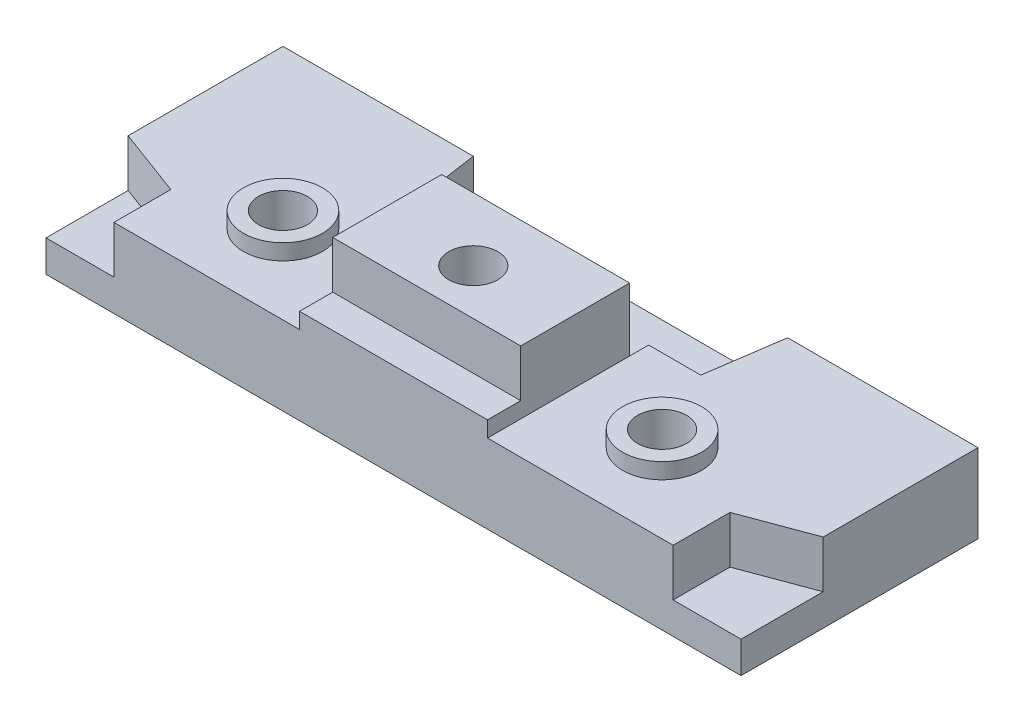
SolidWorks part; units mm, degrees
ref_plane "Front Plane" through (0, 0, 0) normal (0, 0, 1) x (1, 0, 0)
ref_plane "Top Plane" through (0, 0, 0) normal (0, 1, 0) x (1, 0, 0)
ref_plane "Right Plane" through (0, 0, 0) normal (1, 0, 0) x (0, 0, -1)
sketch "Sketch1" plane through (0, 0, 0) normal (0, 1, 0) x (1, 0, 0)
  line L1 (0, 0) -> (44, 0)
  line L2 (0, 0) -> (0, -15)
  line L3 (0, -15) -> (44, -15)
  line L4 (44, 0) -> (44, -15)
  dimension "D1" = 15
  dimension "D2" = 44
extrude "Boss-Extrude1" add sketch "Sketch1" along normal blind 5
sketch "Sketch2" plane through (0, 5, 0) normal (0, 1, 0) x (1, 0, 0)
  line L0 (44, 0) -> (0, 0) construction
  line L1 (16.05, 0) -> (27.95, 0)
  line L2 (16.05, 0) -> (16.05, -15)
  line L3 (16.05, -15) -> (27.95, -15)
  line L4 (27.95, 0) -> (27.95, -15)
  line L5 (0, -15) -> (44, -15) construction
  line L6 (22, 0) -> (22, -15) construction
  dimension "D1" = 5.95
  dimension "D2" = 5.95
extrude "Boss-Extrude2" add sketch "Sketch2" along normal blind 4
sketch "Sketch3" plane through (0, 5, 0) normal (0, 1, 0) x (1, 0, 0)
  line L0 (0, -15) -> (16.05, -15) construction
  line L1 (16.05, 0) -> (16.05, -15) construction
  line L2 (27.95, -15) -> (27.95, 0) construction
  line L3 (27.95, -15) -> (44, -15) construction
  circle A0 centre (10, -10) radius 1.55
  circle A1 centre (34, -10) radius 1.55
  dimension "D1" = 3.1
  dimension "D3" = 3.1
  dimension "D2" = 5
  dimension "D4" = 5
  dimension "D5" = 6.05
  dimension "D6" = 6.05
extrude "Cut-Extrude1" cut sketch "Sketch3" against normal blind 3
sketch "Sketch4" plane through (0, 9, 0) normal (0, 1, 0) x (1, 0, 0)
  line L1 (16.05, -15) -> (27.95, -15) construction
  line L2 (16.05, 0) -> (16.05, -15) construction
  circle A0 centre (22.05, -10) radius 1.55
  dimension "D1" = 3.1
  dimension "D2" = 5
  dimension "D3" = 6
extrude "Cut-Extrude2" cut sketch "Sketch4" against normal blind 3
sketch "Sketch5" plane through (0, 5, 0) normal (0, 1, 0) x (1, 0, 0)
  line L0 (22, 0) -> (22, -15) construction
  line L1 (27.95, 0) -> (16.05, 0) construction
  line L2 (16.05, -15) -> (27.95, -15) construction
  circle A0 centre (10, -10) radius 2.5
  circle A1 centre (10, -10) radius 1.55
  circle A2 centre (34, -10) radius 2.5
  circle A3 centre (34, -10) radius 1.55
  dimension "D1" = 5
extrude "Boss-Extrude3" add sketch "Sketch5" along normal blind 1
sketch "Sketch6" plane through (0, 5, 0) normal (0, 1, 0) x (1, 0, 0)
  line L0 (16.05, -4.8) -> (12.75, -4.8)
  line L1 (16.05, 0) -> (16.05, -15) construction
  line L2 (12.75, -4.8) -> (12.05, 0)
  line L3 (16.05, 0) -> (0, 0) construction
  line L4 (12.05, 0) -> (16.05, 0)
  line L5 (16.05, 0) -> (16.05, -4.8)
  line L6 (0, -15) -> (4.3, -15)
  line L7 (0, -15) -> (16.05, -15) construction
  line L8 (4.3, -15) -> (4.3, -11.4)
  line L9 (4.3, -11.4) -> (0, -9.8)
  line L10 (0, 0) -> (0, -15) construction
  line L11 (0, -9.8) -> (0, -15)
  line L12 (22, 0) -> (22, -15) construction
  line L13 (27.95, 0) -> (16.05, 0) construction
  line L14 (16.05, -15) -> (27.95, -15) construction
  line L15 (39.7, -11.4) -> (44, -9.8)
  line L16 (39.7, -15) -> (39.7, -11.4)
  line L17 (44, -15) -> (39.7, -15)
  line L18 (44, -9.8) -> (44, -15)
  line L19 (31.95, 0) -> (27.95, 0)
  line L20 (31.25, -4.8) -> (31.95, 0)
  line L21 (27.95, -4.8) -> (31.25, -4.8)
  line L22 (27.95, 0) -> (27.95, -4.8)
  dimension "D1" = 4.8
  dimension "D2" = 3.3
  dimension "D3" = 4
  dimension "D4" = 4.3
  dimension "D5" = 3.6
  dimension "D6" = 5.2
extrude "Cut-Extrude3" cut sketch "Sketch6" against normal blind 3
sketch "Sketch7" plane through (0, 9, 0) normal (0, 1, 0) x (1, 0, 0)
  line L0 (27.95, -15) -> (27.95, 0) construction
  line L1 (16.05, 0) -> (27.95, 0)
  line L2 (16.05, 0) -> (16.05, -6)
  line L3 (16.05, -6) -> (27.95, -6)
  line L4 (27.95, 0) -> (27.95, -6)
  dimension "D1" = 6
extrude "Cut-Extrude4" cut sketch "Sketch7" against normal blind 7
sketch "Sketch8" plane through (0, 9, 0) normal (0, 1, 0) x (1, 0, 0)
  line L0 (16.05, -6) -> (16.05, -15) construction
  line L1 (16.05, -12.9) -> (27.95, -12.9)
  line L2 (16.05, -12.9) -> (16.05, -15)
  line L3 (16.05, -15) -> (27.95, -15)
  line L4 (27.95, -12.9) -> (27.95, -15)
  dimension "D1" = 2.1
extrude "Cut-Extrude5" cut sketch "Sketch8" against normal blind 3
